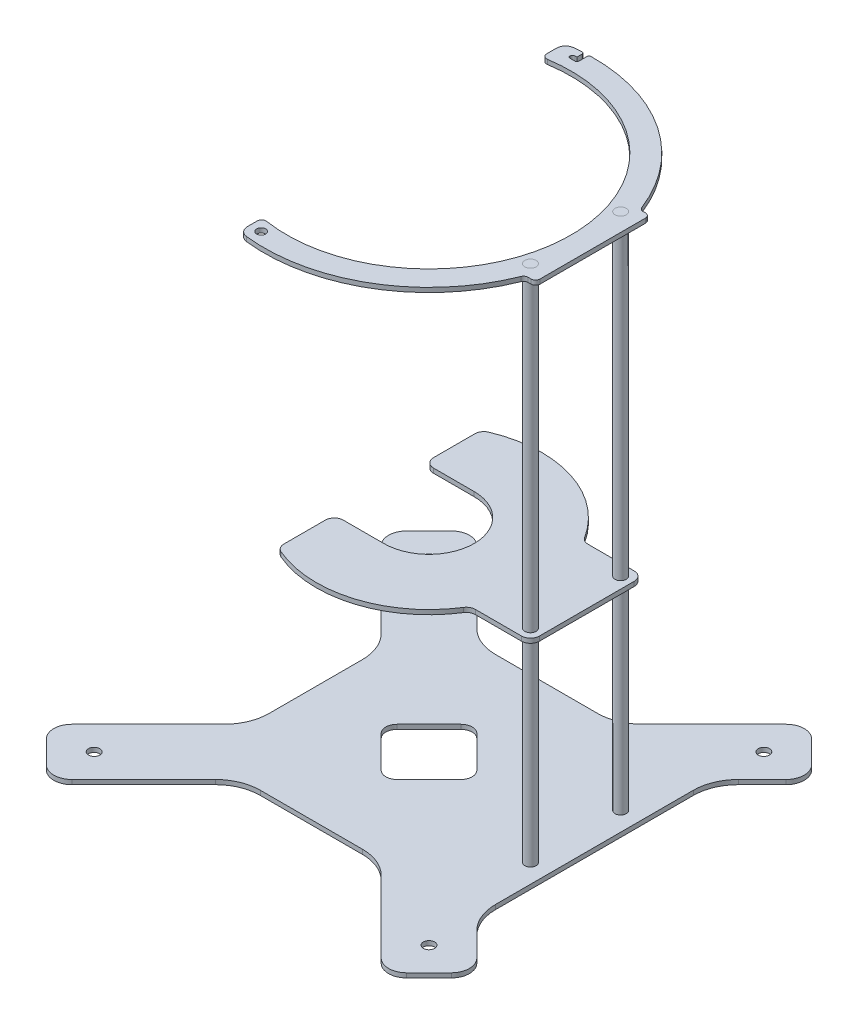
SolidWorks part; units mm, degrees
ref_plane "Front Plane" through (0, 0, 0) normal (0, 0, 1) x (1, 0, 0)
ref_plane "Top Plane" through (0, 0, 0) normal (0, 1, 0) x (1, 0, 0)
ref_plane "Right Plane" through (0, 0, 0) normal (1, 0, 0) x (0, 0, -1)
sketch "main" plane through (0, 0, 0) normal (0, -1, 0) x (0, 0, -1)
  line L0 (44.8999, -22) -> (-44.8999, -22)
  line L1 (20, 0) -> (20, -22)
  line L2 (0, 0) -> (0, 50) construction
  line L4 (0, 50) -> (0, 70) construction
  line L5 (25, 70) -> (-25, 70)
  line L6 (25, 70) -> (25, 37.3266)
  line L7 (25, 37.3266) -> (-25, 37.3266)
  line L8 (-25, 70) -> (-25, 37.3266)
  line L9 (25, 65) -> (-25, 65) construction
  line L10 (-20, 0) -> (-20, -22)
  circle A0 centre (0, 0) radius 50
  circle A1 centre (0, 0) radius 20
  circle A2 centre (0, 0) radius 62 construction
  circle A3 centre (20, 65) radius 2.5
  circle A4 centre (-20, 65) radius 2.5
  point P6 (0, 70)
  dimension "D1" = 100
  dimension "D2" = 40
  dimension "D5" = 124
  dimension "D8" = 5
  dimension "D3" = 22
  dimension "D4" = 50
  dimension "D6" = 20
  dimension "D7" = 5
sketch "Sketch39" plane through (0, 0, 0) normal (0, 1, 0) x (1, 0, 0)
  line L0 (0, -20) -> (-22, -20) construction
  line L1 (0, -20) -> (-18, -20)
  line L3 (70, 25) -> (37.3266, 25) construction
  line L4 (70, 25) -> (70, -25) construction
  line L5 (70, -25) -> (37.3266, -25) construction
  line L6 (0, 20) -> (-22, 20) construction
  line L7 (-22, 44.8999) -> (-22, -44.8999) construction
  line L8 (-22, -24) -> (-22, -42.332)
  line L9 (66, 25) -> (45.5522, 25)
  line L10 (70, 21) -> (70, -21)
  line L11 (66, -25) -> (45.5522, -25)
  line L12 (0, 20) -> (-18, 20)
  line L13 (-22, 42.332) -> (-22, 24)
  arc A0 (-19.5652, -46.0131) -> (42.1779, -26.8519) centre (0, 0) ccw
  circle A1 centre (0, 0) radius 20 construction
  circle A2 centre (65, -20) radius 2.5 construction
  circle A3 centre (65, 20) radius 2.5 construction
  circle A4 centre (0, 0) radius 50 construction
  arc A5 (0, -20) -> (0, 20) centre (0, 0) ccw
  circle A6 centre (65, -20) radius 2.5
  circle A7 centre (65, 20) radius 2.5
  arc A8 (42.1779, 26.8519) -> (-19.5652, 46.0131) centre (0, 0) ccw
  arc A9 (-19.5652, -46.0131) -> (-22, -42.332) centre (-18, -42.332) cw
  arc A10 (-22, -24) -> (-18, -20) centre (-18, -24) cw
  arc A11 (-18, 20) -> (-22, 24) centre (-18, 24) cw
  arc A12 (-22, 42.332) -> (-19.5652, 46.0131) centre (-18, 42.332) cw
  arc A13 (42.1779, -26.8519) -> (45.5522, -25) centre (45.5522, -29) cw
  arc A14 (42.1779, 26.8519) -> (45.5522, 25) centre (45.5522, 29) ccw
  arc A15 (66, -25) -> (70, -21) centre (66, -21) ccw
  arc A16 (66, 25) -> (70, 21) centre (66, 21) cw
  dimension "D1" = 4
  dimension "D2" = 4
  dimension "D3" = 4
base flange "Base-Flange3" sketch "Sketch39" thickness 2 reverse thickness direction no parameters "D1"=2
sketch "Sketch42" plane through (0, 0, 0) normal (0, 1, 0) x (1, 0, 0)
  circle A0 centre (65, -20) radius 2.5 construction
  circle A1 centre (65, -20) radius 2.5
extrude "Boss-Extrude1" add sketch "Sketch42" along normal blind 140 and the other way blind 90 separate body
mirror "Mirror2" about plane through (0, 0, 0) normal (0, 0, 1) of bodies 113
ref_plane "Plane2" through (0, 140, 0) normal (0, 1, 0) x (1, 0, 0)
sketch "Sketch47" plane through (0, 140, 0) normal (0, 1, 0) x (1, 0, 0)
  line L0 (-12, 68.5347) -> (-12, 64.2262)
  line L2 (70, 25) -> (37.3266, 25) construction
  line L4 (73, 23) -> (73, -23.7397)
  line L5 (71, 25) -> (69.9714, 25)
  line L6 (70, 25) -> (70, -25) construction
  line L7 (-12, -64.2262) -> (-12, -68.5347)
  line L8 (69.6815, -25.7397) -> (71, -25.7397)
  line L9 (50, 0) -> (70, 0) construction
  line L10 (-4.0392, 71.8234) -> (-4.0392, 69.6522)
  line L11 (-4.0392, 67.6522) -> (-2.8392, 67.6522)
  line L12 (-2.0392, 71.9925) -> (-2.0392, 68.4522)
  line L13 (-4.0392, 69.6522) -> (-5, 69.6522)
  line L15 (-4.0392, 67.6522) -> (-5.2, 67.6522)
  line L16 (-6, 68.6522) -> (-6, 68.4522)
  arc A0 (68.1055, 26.28) -> (69.9714, 25) centre (69.9714, 27) ccw
  circle A1 centre (0, 0) radius 73 construction
  arc A2 (-8.4638, -72.5077) -> (67.8233, -27) centre (0, 0) ccw
  circle A3 centre (0, 0) radius 63
  arc A4 (-9.6923, -62.25) -> (-9.6923, 62.25) centre (0, 0) ccw
  circle A5 centre (0, 0) radius 63 construction
  arc A6 (68.1055, 26.28) -> (-1.0536, 72.9924) centre (0, 0) ccw
  arc A7 (73, -23.7397) -> (71, -25.7397) centre (71, -23.7397) cw
  arc A8 (73, 23) -> (71, 25) centre (71, 23) ccw
  arc A9 (67.8233, -27) -> (69.6815, -25.7397) centre (69.6815, -27.7397) cw
  arc A10 (-12, -64.2262) -> (-9.6923, -62.25) centre (-10, -64.2262) cw
  arc A11 (-9.6923, 62.25) -> (-12, 64.2262) centre (-10, 64.2262) cw
  arc A12 (-8.4638, -72.5077) -> (-12, -68.5347) centre (-8, -68.5347) cw
  arc A13 (-12, 68.5347) -> (-8.4638, 72.5077) centre (-8, 68.5347) cw
  circle A14 centre (65, 20) radius 2.5 construction
  circle A15 centre (65, -20) radius 2.5 construction
  circle A16 centre (65, 20) radius 2.5
  circle A17 centre (65, -20) radius 2.5
  circle A18 centre (69, 0) radius 2.5 construction
  circle A19 centre (-7.0824, -67.3506) radius 2
  arc A20 (-5.1092, 72.821) -> (-8.4638, 72.5077) centre (0, 0) ccw
  arc A21 (-6, 68.6522) -> (-5, 69.6522) centre (-5, 68.6522) cw
  arc A22 (-1.0536, 72.9924) -> (-2.0392, 71.9925) centre (-1.0392, 71.9925) ccw
  arc A23 (-4.0392, 71.8234) -> (-5.1092, 72.821) centre (-5.0392, 71.8234) ccw
  arc A24 (-5.2, 67.6522) -> (-6, 68.4522) centre (-5.2, 68.4522) cw
  arc A25 (-2.0392, 68.4522) -> (-2.8392, 67.6522) centre (-2.8392, 68.4522) cw
  point P4 (60.2472, 18.4194)
  point P9 (71, 0)
  point P29 (-12, -61.8466)
  point P57 (-6, 69.6522)
  point P62 (-4.0392, 72.8882)
  point P65 (-6, 67.6522)
  dimension "D4" = 2
  dimension "D5" = 4
  dimension "D7" = 2
  dimension "D8" = 4
  dimension "D9" = 10
  dimension "D10" = 1
  dimension "D13" = 0.8
  dimension "D2" = 12
  dimension "D6" = 3
  dimension "D11" = 2
  dimension "D12" = 2
  dimension "D1" = 1
  dimension "D3" = 10
base flange "Base-Flange5" sketch "Sketch47" thickness 2 reverse thickness direction no parameters "D1"=2
sketch "Sketch48" plane through (0, -90, 0) normal (0, -1, 0) x (1, 0, 0)
  line L0 (0, 0) -> (84.8528, 84.8528) construction
  line L1 (10.6066, -10.6066) -> (17.6777, -3.5355)
  line L3 (-10.6066, 10.6066) -> (-3.5355, 17.6777)
  line L4 (79.9031, 89.8026) -> (89.8026, 79.9031)
  line L5 (-22.6454, -52.1429) -> (22.6454, -52.1429)
  line L6 (-73.3561, -52.1429) -> (-73.3561, 52.1429) construction
  line L7 (-22.6454, 52.1429) -> (22.6454, 52.1429)
  line L8 (73.3561, -43.8586) -> (73.3561, 43.8586)
  line L9 (-73.3561, -52.1429) -> (73.3561, 52.1429) construction
  line L10 (-73.3561, 52.1429) -> (73.3561, -52.1429) construction
  line L12 (10.6066, -10.6066) -> (95.4594, 74.2462) construction
  line L13 (-10.6066, 10.6066) -> (74.2462, 95.4594) construction
  line L14 (10.6066, 10.6066) -> (17.6777, 3.5355)
  line L15 (89.8026, -79.9031) -> (79.9031, -89.8026)
  line L16 (-10.6066, -10.6066) -> (-3.5355, -17.6777)
  line L17 (10.6066, -10.6066) -> (3.5355, -17.6777)
  line L18 (-79.9031, -89.8026) -> (-89.8026, -79.9031)
  line L19 (-10.6066, 10.6066) -> (-17.6777, 3.5355)
  line L20 (-10.6066, -10.6066) -> (-17.6777, -3.5355)
  line L21 (-89.8026, 79.9031) -> (-79.9031, 89.8026)
  line L22 (10.6066, 10.6066) -> (3.5355, 17.6777)
  line L23 (-50.2046, 20.7071) -> (-50.2046, -20.7071)
  line L24 (-56.0624, 34.8492) -> (-89.8026, 68.5894)
  line L25 (-56.0624, -34.8492) -> (-89.8026, -68.5894)
  line L26 (-36.7876, -58.0008) -> (-68.5894, -89.8026)
  line L27 (36.7876, -58.0008) -> (68.5894, -89.8026)
  line L28 (79.214, -58.0008) -> (89.8026, -68.5894)
  line L29 (79.214, 58.0008) -> (89.8026, 68.5894)
  line L30 (36.7876, 58.0008) -> (68.5894, 89.8026)
  line L31 (-36.7876, 58.0008) -> (-68.5894, 89.8026)
  circle A10 centre (0, 0) radius 90 construction
  arc A11 (89.8026, 68.5894) -> (89.8026, 79.9031) centre (84.1457, 74.2462) ccw
  arc A12 (79.9031, 89.8026) -> (68.5894, 89.8026) centre (74.2462, 84.1457) ccw
  arc A13 (89.8026, -79.9031) -> (89.8026, -68.5894) centre (84.1457, -74.2462) ccw
  arc A14 (68.5894, -89.8026) -> (79.9031, -89.8026) centre (74.2462, -84.1457) ccw
  arc A15 (-79.9031, -89.8026) -> (-68.5894, -89.8026) centre (-74.2462, -84.1457) ccw
  arc A16 (-89.8026, -68.5894) -> (-89.8026, -79.9031) centre (-84.1457, -74.2462) ccw
  arc A17 (-89.8026, 79.9031) -> (-89.8026, 68.5894) centre (-84.1457, 74.2462) ccw
  arc A18 (-68.5894, 89.8026) -> (-79.9031, 89.8026) centre (-74.2462, 84.1457) ccw
  arc A19 (79.214, 58.0008) -> (73.3561, 43.8586) centre (93.3561, 43.8586) ccw
  arc A20 (73.3561, -43.8586) -> (79.214, -58.0008) centre (93.3561, -43.8586) ccw
  arc A21 (36.7876, -58.0008) -> (22.6454, -52.1429) centre (22.6454, -72.1429) ccw
  arc A22 (36.7876, 58.0008) -> (22.6454, 52.1429) centre (22.6454, 72.1429) cw
  arc A23 (-22.6454, -52.1429) -> (-36.7876, -58.0008) centre (-22.6454, -72.1429) ccw
  arc A24 (-56.0624, -34.8492) -> (-50.2046, -20.7071) centre (-70.2046, -20.7071) ccw
  arc A25 (-50.2046, 20.7071) -> (-56.0624, 34.8492) centre (-70.2046, 20.7071) ccw
  arc A26 (-22.6454, 52.1429) -> (-36.7876, 58.0008) centre (-22.6454, 72.1429) cw
  arc A27 (-3.5355, 17.6777) -> (3.5355, 17.6777) centre (0, 14.1421) cw
  arc A28 (17.6777, 3.5355) -> (17.6777, -3.5355) centre (14.1421, 0) cw
  arc A29 (3.5355, -17.6777) -> (-3.5355, -17.6777) centre (0, -14.1421) cw
  arc A30 (-17.6777, -3.5355) -> (-17.6777, 3.5355) centre (-14.1421, 0) cw
  circle A31 centre (65, 20) radius 2.5 construction
  circle A32 centre (65, -20) radius 2.5 construction
  circle A33 centre (65, 20) radius 2.5
  circle A34 centre (65, -20) radius 2.5
  circle A35 centre (74.2462, 74.2462) radius 2.5
  circle A36 centre (74.2462, -74.2462) radius 2.5
  circle A37 centre (-74.2462, -74.2462) radius 2.5
  circle A38 centre (-74.2462, 74.2462) radius 2.5
  point P48 (0, 0)
  point P60 (30.9297, -52.1429)
  point P63 (30.9297, 52.1429)
  point P66 (-30.9297, -52.1429)
  point P73 (-30.9297, 52.1429)
  point P95 (0, 0)
  dimension "D4" = 8
  dimension "D5" = 4
  dimension "D6" = 20
  dimension "D1" = 120
  dimension "D7" = 5
  dimension "D8" = 15
  dimension "D2" = 15
  dimension "D3" = 15
base flange "Base-Flange7" sketch "Sketch48" thickness 2 reverse thickness direction yes parameters "D1"=2
sketch "Bend-Lines1" [suppressed] plane through (0, 0, 0) normal (0, 1, 0) x (1, 0, 0)
sketch "Bounding-Box1" [suppressed] plane through (0, 0, 0) normal (0, 1, 0) x (1, 0, 0)
sheet metal parameters "Sheet-Metal12" thickness 2 parameters "D1"=2
flat pattern "Flat-Pattern12" [suppressed]
sketch "Bend-Lines5" plane through (0, 0, 0) normal (0, 1, 0) x (1, 0, 0)
sketch3d "Bounding-Box5" [suppressed]
  line L0 (-22, 50, 0) -> (-22, -50, 0) construction
  line L1 (70, 50, 0) -> (70, -50, 0) construction
  line L2 (-22, 50, 0) -> (70, 50, 0) construction
  line L3 (-22, -50, 0) -> (70, -50, 0) construction
sheet metal parameters "Sheet-Metal17" thickness 2 parameters "D1"=2
flat pattern "Flat-Pattern17"
sketch "Bend-Lines7" plane through (0, 0, 0) normal (0, 1, 0) x (1, 0, 0)
sketch3d "Bounding-Box7" [suppressed]
  line L0 (-12, 73, 0) -> (-12, -73, 0) construction
  line L1 (73, 73, 0) -> (73, -73, 0) construction
  line L2 (-12, 73, 0) -> (73, 73, 0) construction
  line L3 (-12, -73, 0) -> (73, -73, 0) construction
sheet metal parameters "Sheet-Metal20" thickness 2 parameters "D1"=2
flat pattern "Flat-Pattern20"
sketch "Bend-Lines9" plane through (0, 0, 0) normal (0, 1, 0) x (1, 0, 0)
sketch3d "Bounding-Box9" [suppressed]
  line L0 (-176.2914, 166.3919, 0) -> (8, 166.3919, 0) construction
  line L1 (-176.2914, -17.8995, 0) -> (8, -17.8995, 0) construction
  line L2 (-176.2914, 166.3919, 0) -> (-176.2914, -17.8995, 0) construction
  line L3 (8, 166.3919, 0) -> (8, -17.8995, 0) construction
